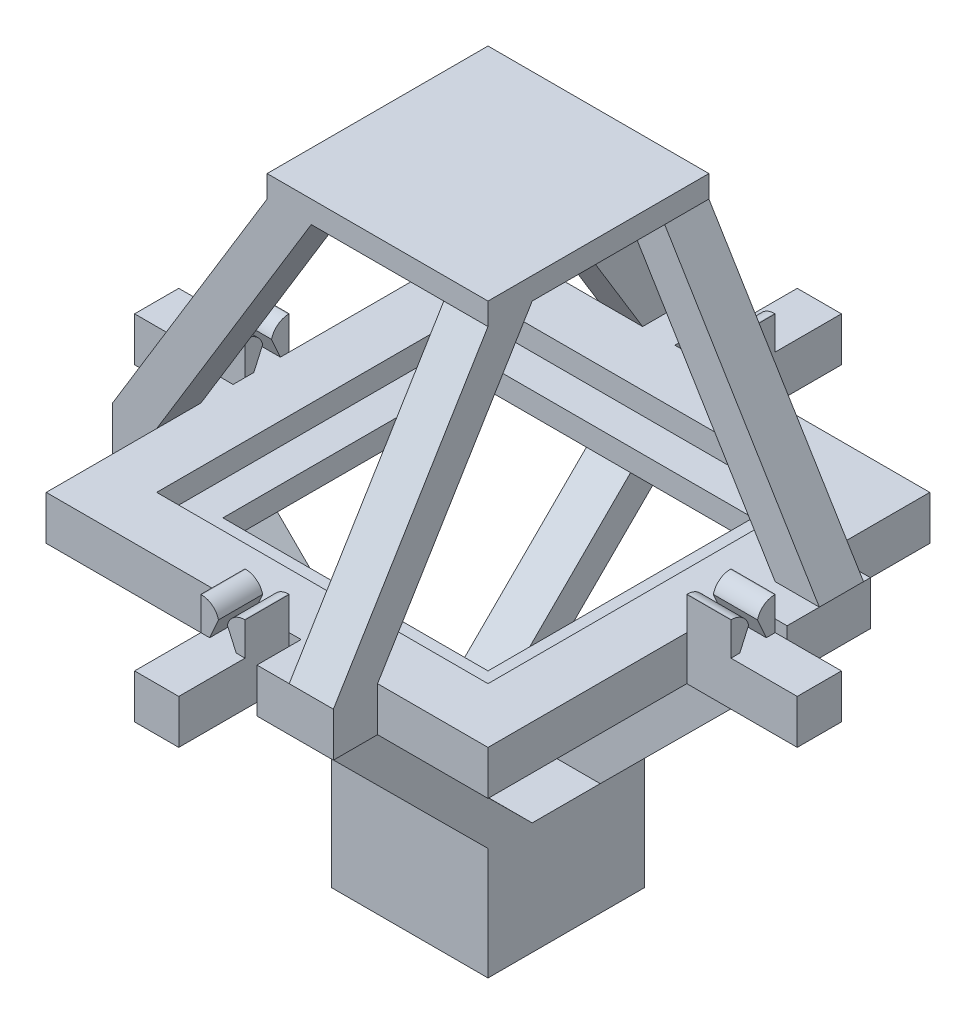
SolidWorks part; units mm, degrees
material "Delrin 2700 NC010, Low Viscosity Acetal Copolymer (SS)"
ref_plane "Front Plane" through (0, 0, 0) normal (0, 0, 1) x (1, 0, 0)
ref_plane "Top Plane" through (0, 0, 0) normal (0, 1, 0) x (1, 0, 0)
ref_plane "Right Plane" through (0, 0, 0) normal (1, 0, 0) x (0, 0, -1)
sketch "Sketch2" plane through (0, 0, 0) normal (0, 1, 0) x (1, 0, 0)
  line L1 (-50, -50) -> (50, -50)
  line L2 (-50, -50) -> (-50, 50)
  line L3 (-50, 50) -> (50, 50)
  line L4 (50, -50) -> (50, 50)
  line L5 (-50, -50) -> (50, 50) construction
  line L6 (-50, 50) -> (50, -50) construction
  point P0 (0, 0)
extrude "Boss-Extrude1" add sketch "Sketch2" along normal blind 5
sketch "Sketch3" plane through (0, 0, 0) normal (0, -1, 0) x (1, 0, 0)
  line L1 (-50, -50) -> (50, -50)
  line L2 (-50, -50) -> (-50, 50)
  line L3 (-50, 50) -> (50, 50)
  line L4 (50, -50) -> (50, 50)
  line L5 (-50, -50) -> (50, 50) construction
  line L6 (-50, 50) -> (50, -50) construction
  point P0 (0, 0)
extrude "Boss-Extrude2" add sketch "Sketch3" along normal blind 5
sketch "Sketch8" plane through (0, -5, 0) normal (0, -1, 0) x (1, 0, 0)
  circle A0 centre (0, 0) radius 5
extrude "Boss-Extrude7" add sketch "Sketch8" along normal blind 30
sketch "Sketch11" plane through (50, 0, 0) normal (1, 0, 0) x (0, 0, -1)
  line L0 (5, -5) -> (5, 12.5)
  line L3 (-5, -5) -> (5, -5)
  line L5 (5, 12.5) -> (1, 12.5)
  line L6 (1, 12.5) -> (1, 9.5)
  line L7 (-5, -5) -> (-5, 12.5)
  line L8 (-5, 12.5) -> (-1, 12.5)
  line L9 (-1, 12.5) -> (-1, 9.5)
  line L10 (-50, 5) -> (50, 5) construction
  line L11 (-1, 9.5) -> (-3, 5)
  line L12 (-3, 5) -> (3, 5)
  line L13 (3, 5) -> (1, 9.5)
  point P0 (0, 0)
  point P8 (3, 5)
  point P12 (-3, 5)
extrude "Boss-Extrude21" add sketch "Sketch11" along normal blind 10
fillet "Fillet14" radius 4 1 edges at (55, 12.5, -1)
fillet "Fillet13" radius 4 1 edges at (55, 12.5, 1)
sketch "Sketch24" plane through (60, 0, 0) normal (1, 0, 0) x (0, 0, -1)
  line L1 (-5, 5) -> (5, 5)
  line L2 (-5, 5) -> (-5, -5)
  line L3 (-5, -5) -> (5, -5)
  line L4 (5, 5) -> (5, -5)
  line L5 (-5, 5) -> (5, -5) construction
  line L6 (-5, -5) -> (5, 5) construction
  point P0 (0, 0)
extrude "Boss-Extrude22" add sketch "Sketch24" along normal blind 15
sketch "Sketch13" plane through (-50, 0, 0) normal (-1, 0, 0) x (0, 0, 1)
  line L0 (50, -5) -> (-50, -5) construction
  line L2 (-5, 12.5) -> (-5, -5)
  line L3 (-5, -5) -> (5, -5)
  line L4 (5, 12.5) -> (5, -5)
  line L5 (5, 12.5) -> (1, 12.5)
  line L6 (1, 12.5) -> (1, 9.5)
  line L7 (-5, 12.5) -> (-1, 12.5)
  line L8 (-1, 12.5) -> (-1, 9.5)
  line L9 (-1, 9.5) -> (-3, 5)
  line L10 (-3, 5) -> (3, 5)
  line L11 (3, 5) -> (1, 9.5)
  point P0 (0, 0)
  point P8 (-3, 5)
  point P13 (3, 5)
extrude "Boss-Extrude25" add sketch "Sketch13" along normal blind 10
sketch "Sketch26" plane through (-60, 0, 0) normal (-1, 0, 0) x (0, 0, 1)
  line L0 (-5, -5) -> (5, -5) construction
  line L1 (-5, 5) -> (5, 5)
  line L2 (-5, 5) -> (-5, -5)
  line L3 (-5, -5) -> (5, -5)
  line L4 (5, 5) -> (5, -5)
  line L5 (-5, 5) -> (5, -5) construction
  line L6 (-5, -5) -> (5, 5) construction
  line L7 (-5, -5) -> (5, -5) construction
  point P0 (0, 0)
extrude "Boss-Extrude26" add sketch "Sketch26" along normal blind 15
fillet "Fillet18" radius 4 1 edges at (-55, 12.5, 1)
fillet "Fillet17" radius 4 1 edges at (-55, 12.5, -1)
sketch "Sketch14" plane through (0, 0, -50) normal (0, 0, -1) x (-1, 0, 0)
  line L0 (-5, 12.5) -> (-1, 12.5)
  line L2 (-5, 12.5) -> (-5, -5)
  line L3 (-5, -5) -> (5, -5)
  line L4 (5, 12.5) -> (5, -5)
  line L5 (5, 12.5) -> (1, 12.5)
  line L6 (-1, 12.5) -> (-1, 9.5)
  line L7 (1, 12.5) -> (1, 9.5)
  line L8 (-50, 5) -> (50, 5) construction
  line L9 (-1, 9.5) -> (-3, 5)
  line L10 (-3, 5) -> (3, 5)
  line L11 (3, 5) -> (1, 9.5)
  point P0 (0, 0)
  point P11 (3, 5)
  point P12 (-3, 5)
extrude "Boss-Extrude23" add sketch "Sketch14" along normal blind 10
sketch "Sketch25" plane through (0, 0, -60) normal (0, 0, -1) x (-1, 0, 0)
  line L1 (-5, 5) -> (5, 5)
  line L2 (-5, 5) -> (-5, -5)
  line L3 (-5, -5) -> (5, -5)
  line L4 (5, 5) -> (5, -5)
  line L5 (-5, 5) -> (5, -5) construction
  line L6 (-5, -5) -> (5, 5) construction
  point P0 (0, 0)
extrude "Boss-Extrude24" add sketch "Sketch25" along normal blind 15
fillet "Fillet15" radius 4 1 edges at (-1, 12.5, -55)
fillet "Fillet16" radius 4 1 edges at (1, 12.5, -55)
sketch "Sketch12" plane through (0, 0, 50) normal (0, 0, 1) x (1, 0, 0)
  line L0 (50, -5) -> (-50, -5) construction
  line L2 (-5, 12.5) -> (-5, -5)
  line L3 (-5, -5) -> (5, -5)
  line L4 (5, 12.5) -> (5, -5)
  line L5 (5, 12.5) -> (1, 12.5)
  line L6 (1, 12.5) -> (1, 9.5)
  line L7 (-5, -5) -> (5, -5) construction
  line L8 (-5, 12.5) -> (-1, 12.5)
  line L9 (-1, 12.5) -> (-1, 9.5)
  line L10 (-1, 9.5) -> (-3, 5)
  line L11 (-3, 5) -> (3, 5)
  line L12 (3, 5) -> (1, 9.5)
  point P0 (0, 0)
  point P10 (-3, 5)
  point P15 (3, 5)
extrude "Boss-Extrude10" add sketch "Sketch12" along normal blind 10
fillet "Fillet19" radius 4 1 edges at (-1, 12.5, 55)
sketch "Sketch27" plane through (0, 0, 60) normal (0, 0, 1) x (1, 0, 0)
  line L1 (-5, 5) -> (5, 5)
  line L2 (-5, 5) -> (-5, -5)
  line L3 (-5, -5) -> (5, -5)
  line L4 (5, 5) -> (5, -5)
  line L5 (-5, 5) -> (5, -5) construction
  line L6 (-5, -5) -> (5, 5) construction
  point P0 (0, 0)
extrude "Boss-Extrude27" add sketch "Sketch27" along normal blind 15
fillet "Fillet20" radius 4 1 edges at (1, 12.5, 55)
ref_plane "Plane4" through (0, 72.5, 0) normal (0, 1, 0) x (1, 0, 0)
ref_plane "Plane5" through (0, -72.5, 0) normal (0, 1, 0) x (1, 0, 0)
sketch "Sketch62" plane through (0, -5, 0) normal (0, -1, 0) x (1, 0, 0)
  circle A0 centre (0, 0) radius 11.2235
extrude "Cut-Extrude3" cut sketch "Sketch62" along normal blind 30
sketch "Sketch64" plane through (0, -72.5, 0) normal (0, 1, 0) x (1, 0, 0)
  line L2 (17.7, 17.7) -> (-17.7, 17.7)
  line L3 (17.7, 17.7) -> (17.7, -17.7)
  line L4 (17.7, -17.7) -> (-17.7, -17.7)
  line L5 (-17.7, 17.7) -> (-17.7, -17.7)
  line L6 (17.7, 17.7) -> (-17.7, -17.7) construction
  line L7 (17.7, -17.7) -> (-17.7, 17.7) construction
  point P1 (0, 0)
extrude "Boss-Extrude53" add sketch "Sketch64" along normal blind 25.4 separate body
sketch "Sketch66" plane through (0, -72.5, 0) normal (0, -1, 0) x (-1, 0, 0)
  line L1 (12.7, -12.7) -> (-12.7, -12.7)
  line L2 (12.7, -12.7) -> (12.7, 12.7)
  line L3 (12.7, 12.7) -> (-12.7, 12.7)
  line L4 (-12.7, -12.7) -> (-12.7, 12.7)
  line L5 (12.7, -12.7) -> (-12.7, 12.7) construction
  line L6 (12.7, 12.7) -> (-12.7, -12.7) construction
  point P0 (0, 0)
extrude "Cut-Extrude4" cut sketch "Sketch66" against normal blind 12.7
ref_plane "Plane6" through (0, 67.5, 0) normal (0, 1, 0) x (1, 0, 0)
sketch "Sketch67" plane through (0, 67.5, 0) normal (0, 1, 0) x (1, 0, 0)
  line L1 (-25, 25) -> (25, 25)
  line L2 (-25, 25) -> (-25, -25)
  line L3 (-25, -25) -> (25, -25)
  line L4 (25, 25) -> (25, -25)
  line L5 (-25, 25) -> (25, -25) construction
  line L6 (-25, -25) -> (25, 25) construction
  point P0 (0, 0)
extrude "Boss-Extrude54" add sketch "Sketch67" against normal blind 5 separate body
sketch "Sketch68" plane through (0, 0, 50) normal (0, 0, 1) x (1, 0, 0)
  line L0 (5, 5) -> (50, 5) construction
  line L1 (50, -5) -> (5, -5) construction
  line L2 (7.7, -5) -> (25, -5)
  line L3 (25, -5) -> (25, 5)
  line L4 (25, 5) -> (7.7, 5)
  line L5 (7.7, 5) -> (7.7, -5)
  point P0 (25, 5)
  point P1 (15, 5)
  point P4 (15, 5)
  point P5 (17.7, -5)
  point P6 (7.7, -5)
extrude "Boss-Extrude55" add sketch "Sketch68" along normal blind 10
sketch "Sketch69" plane through (50, 0, 0) normal (1, 0, 0) x (0, 0, -1)
  line L0 (5, 5) -> (50, 5) construction
  line L1 (26.5525, 5) -> (9.2525, 5)
  line L2 (9.2525, -5) -> (9.2525, 5)
  line L3 (50, -5) -> (5, -5) construction
  line L4 (9.2525, -5) -> (26.5525, -5)
  line L5 (26.5525, -5) -> (26.5525, 5)
  point P0 (26.5525, 5)
extrude "Boss-Extrude56" add sketch "Sketch69" along normal blind 10
sketch "Sketch70" plane through (0, 0, -50) normal (0, 0, -1) x (-1, 0, 0)
  line L0 (5, 5) -> (50, 5) construction
  line L1 (25, 5) -> (7.7, 5)
  line L2 (7.7, 5) -> (7.7, -5)
  line L3 (50, -5) -> (5, -5) construction
  line L4 (7.7, -5) -> (25, -5)
  line L5 (25, -5) -> (25, 5)
  point P0 (25, 5)
extrude "Boss-Extrude57" add sketch "Sketch70" along normal blind 10
sketch "Sketch74" plane through (-50, 0, 0) normal (-1, 0, 0) x (0, 0, 1)
  line L0 (5, 5) -> (50, 5) construction
  line L1 (25, 5) -> (7.7, 5)
  line L2 (7.7, 5) -> (7.7, -5)
  line L3 (50, -5) -> (5, -5) construction
  line L4 (7.7, -5) -> (25, -5)
  line L5 (25, -5) -> (25, 5)
  point P0 (25, 5)
extrude "Boss-Extrude58" add sketch "Sketch74" along normal blind 10
sketch "Sketch76" plane through (-17.7, 0, 0) normal (-1, 0, 0) x (0, 0, 1)
  line L0 (-17.7, -47.1) -> (-60, -5)
  line L1 (-60, -5) -> (-50, -5)
  line L2 (-60, -5) -> (-50, -5) construction
  line L3 (-50, -5) -> (-7.7, -47.1)
  line L4 (-17.7, -47.1) -> (17.7, -47.1) construction
  line L5 (-7.7, -47.1) -> (-17.7, -47.1)
extrude "Boss-Extrude59" add sketch "Sketch76" against normal blind 10
sketch "Sketch77" plane through (-25, 0, 0) normal (-1, 0, 0) x (0, 0, 1)
  line L0 (-25, 62.5) -> (-60, 5)
  line L1 (-60, 5) -> (-50, 5)
  line L2 (-25, 62.5) -> (-15, 62.5)
  line L3 (-25, 62.5) -> (25, 62.5) construction
  line L4 (-15, 62.5) -> (-50, 5)
extrude "Boss-Extrude60" add sketch "Sketch77" against normal blind 10
sketch "Sketch78" plane through (0, 0, 17.7) normal (0, 0, 1) x (1, 0, 0)
  line L0 (-17.7, -47.1) -> (-60, -5)
  line L1 (-60, -5) -> (-50, -5)
  line L2 (-50, -5) -> (-7.7, -47.1)
  line L3 (-7.7, -47.1) -> (-17.7, -47.1)
extrude "Boss-Extrude61" add sketch "Sketch78" against normal blind 10
sketch "Sketch79" plane through (0, 0, 25) normal (0, 0, 1) x (1, 0, 0)
  line L0 (-25, 62.5) -> (-60, 5)
  line L1 (-60, 5) -> (-50, 5)
  line L2 (-50, 5) -> (-15, 62.5)
  line L3 (-15, 62.5) -> (-25, 62.5)
extrude "Boss-Extrude62" add sketch "Sketch79" against normal blind 10
sketch "Sketch82" plane through (17.7, 0, 0) normal (1, 0, 0) x (0, 0, -1)
  line L0 (-60, -5) -> (-17.7, -47.1)
  line L1 (-17.7, -47.1) -> (-7.7, -47.1)
  line L2 (-7.7, -47.1) -> (-50, -5)
  line L3 (-50, -5) -> (-60, -5)
extrude "Boss-Extrude63" add sketch "Sketch82" against normal blind 10
sketch "Sketch83" plane through (25, 0, 0) normal (1, 0, 0) x (0, 0, -1)
  line L0 (-25, 62.5) -> (-60, 5)
  line L1 (-60, 5) -> (-50, 5)
  line L2 (-50, 5) -> (-15, 62.5)
  line L3 (-15, 62.5) -> (-25, 62.5)
extrude "Boss-Extrude64" add sketch "Sketch83" against normal blind 10
sketch "Sketch85" plane through (50, 0, 0) normal (1, 0, 0) x (0, 0, -1)
  line L0 (5, 5) -> (9.2525, 5) construction
  line L1 (25, 5) -> (7.7, 5)
  line L2 (7.7, 5) -> (7.7, -5)
  line L4 (50, -5) -> (26.5525, -5) construction
  line L5 (7.7, -5) -> (25, -5)
  line L6 (25, -5) -> (25, 5)
  point P0 (25, 5)
extrude "Boss-Extrude65" add sketch "Sketch85" along normal blind 10
sketch "Sketch86" plane through (0, 0, -25) normal (0, 0, -1) x (-1, 0, 0)
  line L0 (-25, 62.5) -> (-60, 5)
  line L1 (-60, 5) -> (-50, 5)
  line L2 (-50, 5) -> (-15, 62.5)
  line L3 (-15, 62.5) -> (-25, 62.5)
extrude "Boss-Extrude66" add sketch "Sketch86" against normal blind 10
sketch "Sketch89" plane through (0, 0, -17.7) normal (0, 0, -1) x (-1, 0, 0)
  line L0 (-60, -5) -> (-50, -5)
  line L1 (-50, -5) -> (-7.7, -47.1)
  line L2 (-7.7, -47.1) -> (-17.7, -47.1)
  line L3 (-17.7, -47.1) -> (-60, -5)
extrude "Boss-Extrude67" add sketch "Sketch89" against normal blind 10
sketch "Sketch90" plane through (0, 5, 0) normal (0, 1, 0) x (1, 0, 0)
  line L1 (-37.5, 37.5) -> (37.5, 37.5)
  line L2 (-37.5, 37.5) -> (-37.5, -37.5)
  line L3 (-37.5, -37.5) -> (37.5, -37.5)
  line L4 (37.5, 37.5) -> (37.5, -37.5)
  line L5 (-37.5, 37.5) -> (37.5, -37.5) construction
  line L6 (-37.5, -37.5) -> (37.5, 37.5) construction
  point P0 (0, 0)
extrude "Cut-Extrude5" cut sketch "Sketch90" against normal blind 5
sketch "Sketch91" plane through (0, 5, 0) normal (0, 1, 0) x (1, 0, 0)
  line L1 (-30, 30) -> (30, 30)
  line L2 (-30, 30) -> (-30, -30)
  line L3 (-30, -30) -> (30, -30)
  line L4 (30, 30) -> (30, -30)
  line L5 (-30, 30) -> (30, -30) construction
  line L6 (-30, -30) -> (30, 30) construction
  point P0 (0, 0)
extrude "Cut-Extrude6" cut sketch "Sketch91" against normal blind 10
